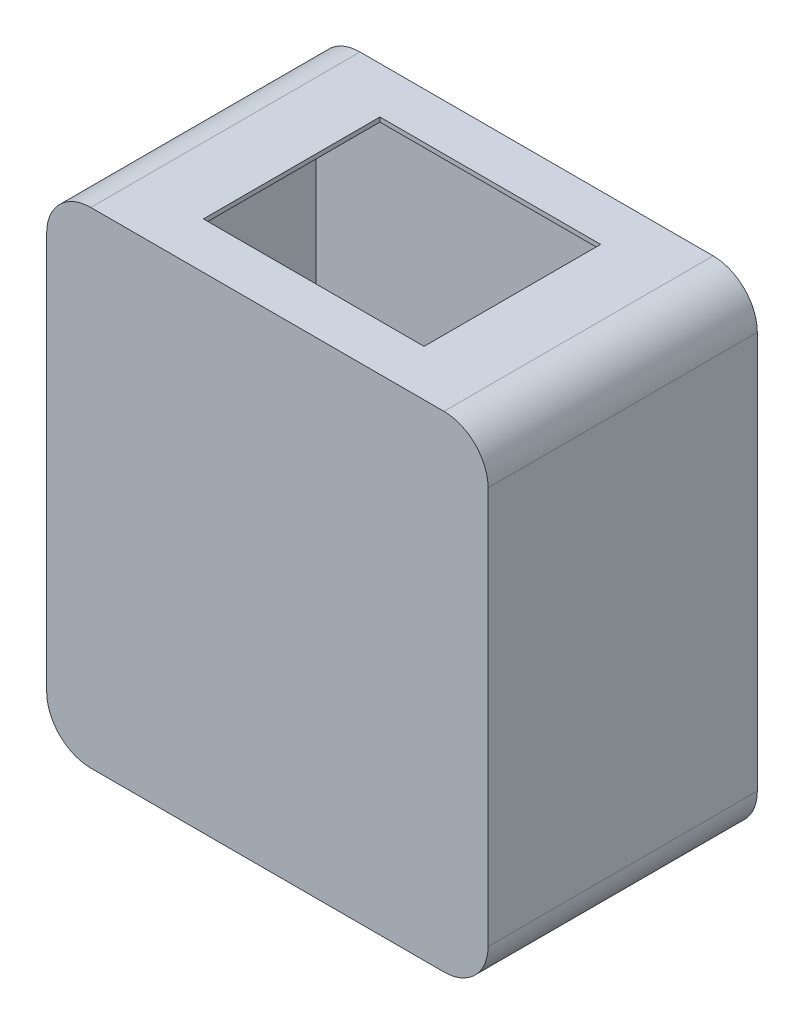
SolidWorks part; units mm, degrees
ref_plane "Front Plane" through (0, 0, 0) normal (0, 0, 1) x (1, 0, 0)
ref_plane "Top Plane" through (0, 0, 0) normal (0, 1, 0) x (1, 0, 0)
ref_plane "Right Plane" through (0, 0, 0) normal (1, 0, 0) x (0, 0, -1)
sketch "Sketch1" plane through (0, 0, 0) normal (0, 0, 1) x (1, 0, 0)
  line L0 (-96.6152, 124.7537) -> (63.3848, 124.7537)
  line L1 (-98.6152, 126.7537) -> (61.3848, 126.7537)
  line L2 (-118.6152, 106.7537) -> (-118.6152, -73.2463)
  line L4 (81.3848, 106.7537) -> (81.3848, -73.2463)
  line L13 (-116.6152, 104.7537) -> (-116.6152, -71.0526)
  line L18 (-98.6152, -93.2463) -> (61.3848, -93.2463)
  line L19 (79.3848, 108.9474) -> (79.3848, -71.0526)
  line L21 (-110.8263, -85.3201) -> (-16.6152, -91.2463)
  line L22 (-16.6152, -91.2463) -> (75.0695, -84.069)
  arc A1 (-98.6152, 126.7537) -> (-118.6152, 106.7537) centre (-98.6152, 106.7537) ccw
  arc A2 (61.3848, 126.7537) -> (81.3848, 106.7537) centre (61.3848, 106.7537) cw
  arc A5 (61.3848, -93.2463) -> (81.3848, -73.2463) centre (61.3848, -73.2463) ccw
  arc A6 (-98.6152, -93.2463) -> (-118.6152, -73.2463) centre (-98.6152, -73.2463) cw
  arc A7 (-96.6152, 124.7537) -> (-116.6152, 104.7537) centre (-96.6152, 104.7537) ccw
  arc A8 (63.3848, 124.7537) -> (79.3848, 108.9474) centre (59.7613, 105.0847) cw
  arc A9 (75.0695, -84.069) -> (79.3848, -71.0526) centre (59.3936, -71.6486) ccw
  arc A10 (-110.8263, -85.3201) -> (-116.6152, -71.0526) centre (-96.6162, -71.2463) cw
  point P0 (0, 0)
  point P3 (-111.0442, 2.1937)
  point P6 (0.6283, -0.5654)
  point P14 (-110.416, 1.6282)
  dimension "D3" = 40
  dimension "D4" = 40
  dimension "D1" = 220
  dimension "D2" = 200
  dimension "D5" = 2
  dimension "D6" = 196
extrude "Boss-Extrude1" add sketch "Sketch1" along normal blind 120
sketch "Sketch2" plane through (0, 0, 0) normal (0, 0, -1) x (-1, 0, 0)
  line L0 (-81.3848, -73.2463) -> (-81.3848, 106.7537) construction
  line L1 (98.6152, -93.2463) -> (-61.3848, -93.2463) construction
  line L2 (118.6152, 106.7537) -> (118.6152, -73.2463) construction
  line L3 (-61.3848, 126.7537) -> (98.6152, 126.7537) construction
  line L4 (-81.3848, -73.2463) -> (-81.3848, 106.7537)
  line L5 (98.6152, -93.2463) -> (-61.3848, -93.2463)
  line L6 (118.6152, 106.7537) -> (118.6152, -73.2463)
  line L7 (-61.3848, 126.7537) -> (98.6152, 126.7537)
  arc A0 (-61.3848, 126.7537) -> (-81.3848, 106.7537) centre (-61.3848, 106.7537) ccw construction
  arc A1 (-81.3848, -73.2463) -> (-61.3848, -93.2463) centre (-61.3848, -73.2463) ccw construction
  arc A2 (98.6152, -93.2463) -> (118.6152, -73.2463) centre (98.6152, -73.2463) ccw construction
  arc A3 (118.6152, 106.7537) -> (98.6152, 126.7537) centre (98.6152, 106.7537) ccw construction
  arc A4 (-61.3848, 126.7537) -> (-81.3848, 106.7537) centre (-61.3848, 106.7537) ccw
  arc A5 (-81.3848, -73.2463) -> (-61.3848, -93.2463) centre (-61.3848, -73.2463) ccw
  arc A6 (98.6152, -93.2463) -> (118.6152, -73.2463) centre (98.6152, -73.2463) ccw
  arc A7 (118.6152, 106.7537) -> (98.6152, 126.7537) centre (98.6152, 106.7537) ccw
extrude "Boss-Extrude2" add sketch "Sketch2" along normal blind 2
ref_plane "Plane1" through (0, 0, 59) normal (0, 0, 1) x (1, 0, 0)
mirror "Mirror1" about plane through (0, 0, 59) normal (0, 0, 1) of "Boss-Extrude2"
sketch "Sketch4" plane through (0, 0, -2) normal (0, 0, -1) x (-1, 0, 0)
  line L0 (-61.3848, -93.2463) -> (98.6152, -93.2463) construction
  line L1 (18.6152, -93.2463) -> (18.6152, 126.7537) construction
  line L2 (98.6152, 126.7537) -> (-61.3848, 126.7537) construction
  circle A0 centre (18.6152, -88.0713) radius 3.175
  point P8 (0, 0)
  dimension "D1" = 6.35
  dimension "D2" = 5.175
extrude "Cut-Extrude2" cut sketch "Sketch4" against normal blind 2 contours A0
sketch "Sketch5" plane through (0, 126.7537, 0) normal (0, 1, 0) x (1, 0, 0)
  line L0 (-98.6152, 2) -> (61.3848, 2) construction
  line L1 (-68.6152, -19) -> (31.3848, -19)
  line L2 (-68.6152, -19) -> (-68.6152, -99)
  line L3 (-68.6152, -99) -> (31.3848, -99)
  line L4 (31.3848, -19) -> (31.3848, -99)
  line L5 (-68.6152, -19) -> (31.3848, -99) construction
  line L6 (-68.6152, -99) -> (31.3848, -19) construction
  line L8 (-18.6152, -120) -> (-18.6152, 2) construction
  line L9 (61.3848, -120) -> (-98.6152, -120) construction
  line L10 (-98.6152, -59) -> (61.3848, -59) construction
  line L11 (-98.6152, -120) -> (-98.6152, 2) construction
  line L12 (61.3848, -120) -> (61.3848, 2) construction
  point P0 (-18.6152, -59)
  point P17 (0, 0)
  point P18 (0, 0)
  dimension "D1" = 100
  dimension "D2" = 80
extrude "Cut-Extrude3" cut sketch "Sketch5" against normal blind 2
equation "\"wallthickness\"= 0.2cm"
equation "\"height\"= 22cm"
equation "\"width\"= 20cm"
equation "\"D1@Sketch1\"=\"height\""
equation "\"D2@Sketch1\"=\"width\""
equation "\"D5@Sketch1\"=\"wallthickness\""
equation "\"D2@Sketch4\"=\"wallthickness\"+ 0.125in"
